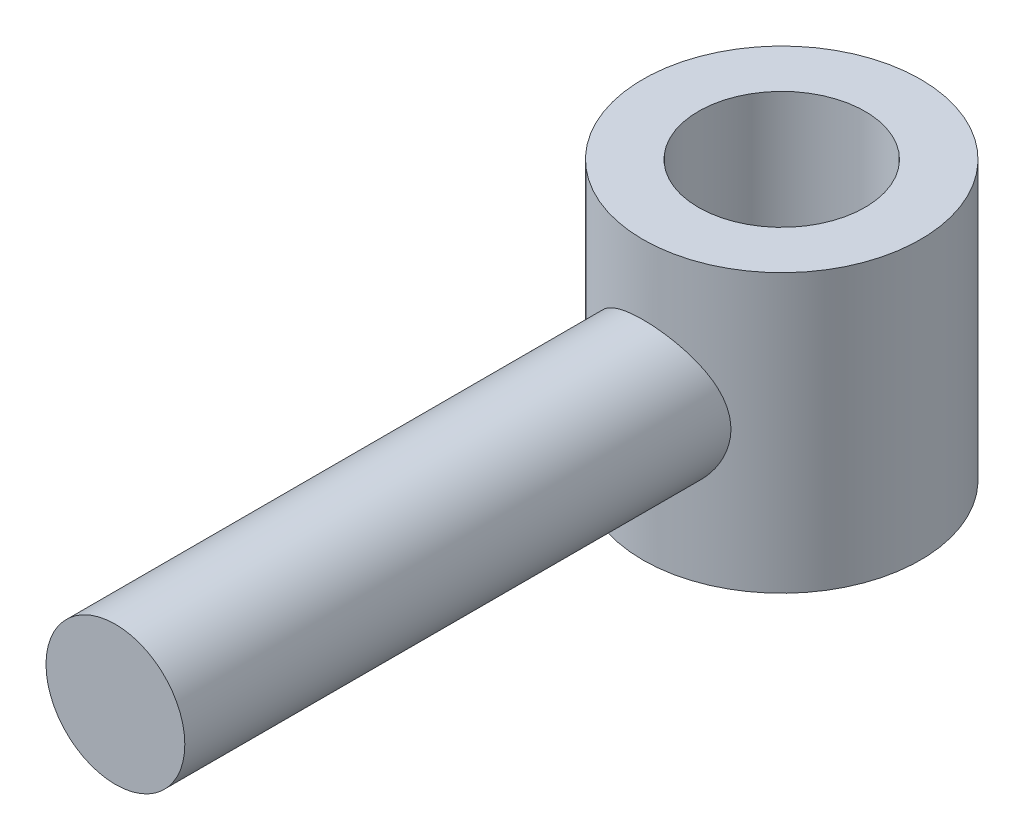
SolidWorks part; units mm, degrees
ref_plane "Front Plane" through (0, 0, 0) normal (0, 0, 1) x (1, 0, 0)
ref_plane "Top Plane" through (0, 0, 0) normal (0, 1, 0) x (1, 0, 0)
ref_plane "Right Plane" through (0, 0, 0) normal (1, 0, 0) x (0, 0, -1)
sketch "Sketch1" plane through (0, 0, 0) normal (0, 1, 0) x (1, 0, 0)
  circle A0 centre (0, 0) radius 7.5
  circle A1 centre (0, 0) radius 12.5
  dimension "D1" = 15
  dimension "D2" = 5
sketch "Sketch2" plane through (0, 0, 0) normal (0, 0, 1) x (1, 0, 0)
  circle A0 centre (0, 0) radius 6.25
  dimension "D1" = 12.5
extrude "Boss-Extrude3" add sketch "Sketch2" along normal blind 60 contours A0
extrude "Boss-Extrude4" add sketch "Sketch1" along normal mid plane 25 contours A1
extrude "Cut-Extrude1" cut sketch "Sketch1<4>" against normal through all both and the other way through all contours A0
sketch "Sketch1<4>" plane through (0, 0, 0) normal (0, 1, 0) x (1, 0, 0) same geometry as "Sketch1"
